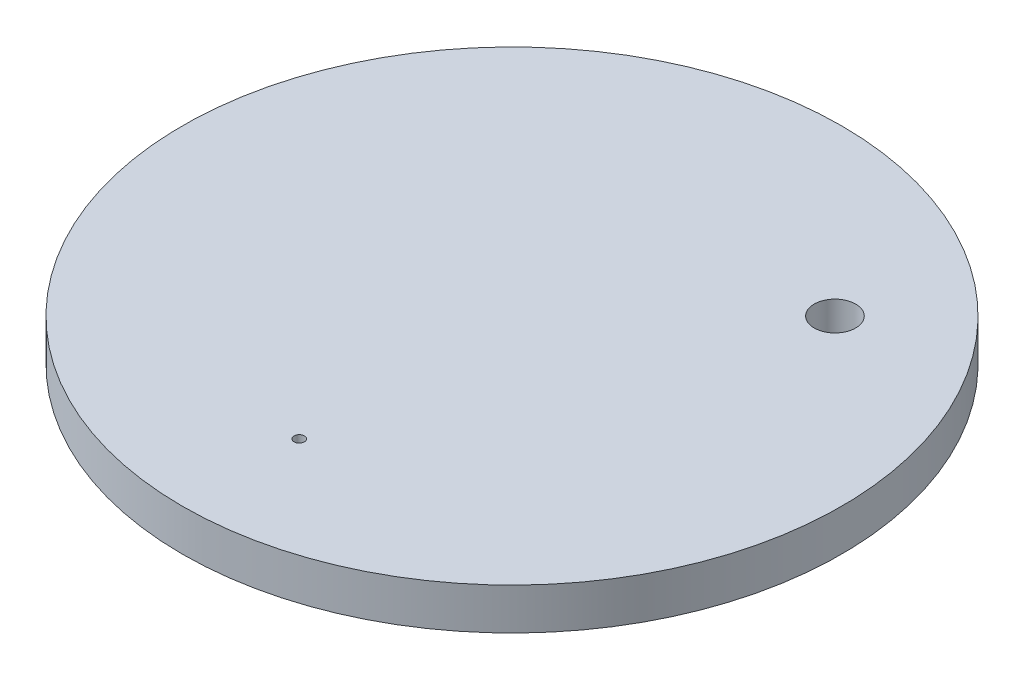
SolidWorks part; units mm, degrees
material "1060 Alloy"
ref_plane "Front Plane" through (0, 0, 0) normal (0, 0, 1) x (1, 0, 0)
ref_plane "Top Plane" through (0, 0, 0) normal (0, 1, 0) x (1, 0, 0)
ref_plane "Right Plane" through (0, 0, 0) normal (1, 0, 0) x (0, 0, -1)
sketch "Sketch1" plane through (0, 0, 0) normal (0, 1, 0) x (1, 0, 0)
  circle A0 centre (0, 0) radius 15.875
  dimension "D1" = 31.75
extrude "Boss-Extrude1" add sketch "Sketch1" along normal blind 1
sketch "Sketch6" plane through (0, 0, 0) normal (0, -1, 0) x (1, 0, 0)
  circle A0 centre (0, 0) radius 15.875
  circle A1 centre (0, 0) radius 8.9
  circle A2 centre (0, 0) radius 15.875 construction
  dimension "D1" = 0
  dimension "D2" = 17.8
extrude "Boss-Extrude3" add sketch "Sketch6" along normal blind 1
thread "Thread1" pitch 0.25 method cut profile "Thread Profile1" start angle 0, offset 0, length 1, pitch 0.25, diameter 17.8
ref_plane "Plane1" through (8.9, -1, 0) normal (0, 0, 1) x (1, 0, 0)
sketch "Thread Profile1" plane through (8.9, -1, 0) normal (0, 0, 1) x (1, 0, 0)
  line L0 (0, 0) -> (0, 0.25) construction
  line L1 (0, 0) -> (0.1353, 0.0781)
  line L2 (0.1353, 0.0781) -> (0.1353, 0.1094)
  line L3 (0.1353, 0.1094) -> (0, 0.1875)
  line L4 (0.1353, 0.0937) -> (0, 0.0937) construction
  line L11 (0, 0) -> (0, 0.1875)
  point P2 (0, 0)
  dimension "Pitch" = 0.25
  dimension "Profile_Angle" = 60
  dimension "Profile_Land" = 0.0312
  dimension "Profile_Height" = 0.1353
sketch "Sketch7" plane through (0, 1, 0) normal (0, 1, 0) x (1, 0, 0)
  circle A0 centre (0, -10.25) radius 0.25
  circle A1 centre (0, 0) radius 9.8
  dimension "D1" = 0.5
  dimension "D2" = 10.25
  dimension "D3" = 19.6
extrude "Cut-Extrude1" cut sketch "Sketch7" against normal through all both and the other way through all contours A1 A0 region at (0, 1, 10.25)
sketch "Sketch8" plane through (0, 1, 0) normal (0, 1, 0) x (1, 0, 0)
  line L0 (0, 0) -> (13.2071, 13.2071) construction
  circle A0 centre (7.7782, 7.7782) radius 1
  dimension "D1" = 2
  dimension "D2" = 11
extrude "Cut-Extrude2" cut sketch "Sketch8" against normal through all both and the other way through all
